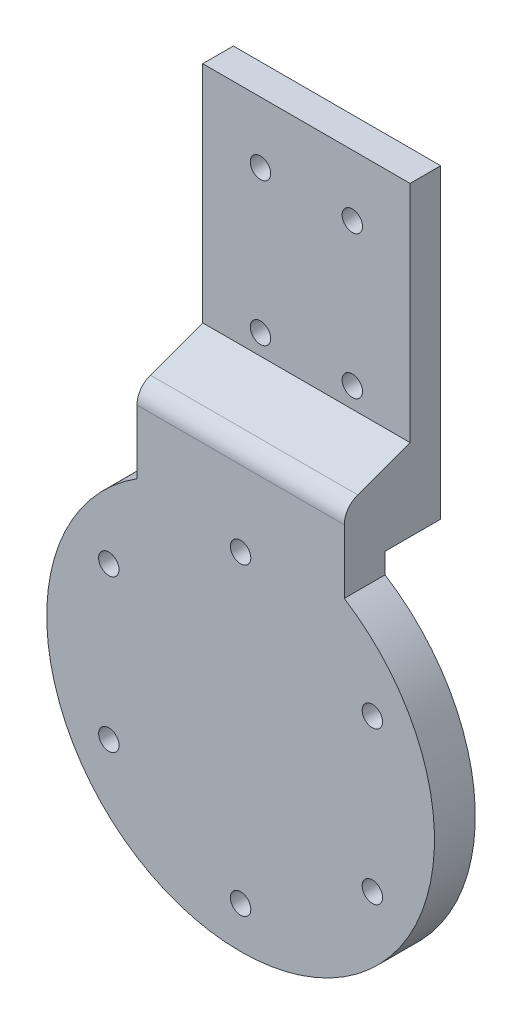
SolidWorks part; units mm, degrees
ref_plane "Front Plane" through (0, 0, 0) normal (0, 0, 1) x (1, 0, 0)
ref_plane "Top Plane" through (0, 0, 0) normal (0, 1, 0) x (1, 0, 0)
ref_plane "Right Plane" through (0, 0, 0) normal (1, 0, 0) x (0, 0, -1)
sketch "Sketch1" plane through (0, 0, 0) normal (0, 0, 1) x (1, 0, 0)
  line L0 (-25.4, 40.1384) -> (-25.4, 120.1384)
  line L1 (-25.4, 120.1384) -> (25.4, 120.1384)
  line L2 (25.4, 120.1384) -> (25.4, 40.1384)
  line L4 (-11.25, 105.1384) -> (11.25, 105.1384) construction
  line L5 (-11.25, 105.1384) -> (-11.25, 70.1384) construction
  line L6 (-11.25, 70.1384) -> (11.25, 70.1384) construction
  line L7 (11.25, 105.1384) -> (11.25, 70.1384) construction
  line L9 (-25.4, 45.1384) -> (25.4, 45.1384)
  line L10 (-25.4, 55.1384) -> (25.4, 55.1384)
  circle A2 centre (-11.25, 105.1384) radius 2.5
  circle A3 centre (11.25, 105.1384) radius 2.5
  circle A4 centre (11.25, 70.1384) radius 2.5
  circle A5 centre (-11.25, 70.1384) radius 2.5
  arc A6 (-25.4, 40.1384) -> (25.4, 40.1384) centre (0, 0) ccw
  circle A8 centre (0, 0) radius 37.28 construction
  circle A9 centre (0, 37.28) radius 2.5
  circle A10 centre (32.2854, 18.64) radius 2.5
  circle A11 centre (32.2854, -18.64) radius 2.5
  circle A12 centre (0, -37.28) radius 2.5
  circle A13 centre (-32.2854, -18.64) radius 2.5
  circle A14 centre (-32.2854, 18.64) radius 2.5
  point P2 (25.4, 40.1384)
  point P3 (0, 0)
  point P13 (0, 70.1384)
  point P32 (0, 0)
  point P35 (-25.4, 0)
  point P36 (-25.4, 0)
  point P37 (25.7058, 8.5415)
  point P38 (-26.525, 0)
  point P39 (0, 0)
  point P40 (0, 120.1384)
  dimension "D1" = 95
  dimension "D4" = 5
  dimension "D8" = 74.56
  dimension "D9" = 5
  dimension "D2" = 50.8
  dimension "D3" = 5
  dimension "D5" = 35
  dimension "D6" = 15
  dimension "D7" = 22.5
  dimension "D11" = 25
  dimension "D12" = 10
  dimension "D10" = 6
extrude "5" add sketch "Sketch1" along normal blind 7.5 contours L0 L9 L2 L1 A5 A4 A3 A2 region at (0, 87.6384, 0)
extrude "Boss-Extrude1" add sketch "Sketch1<3>" along normal blind 13.625 contours L10 L0 L9 L2 region at (0, 50.1384, 0)
sketch "Sketch1<3>" plane through (0, 0, 0) normal (0, 0, 1) x (1, 0, 0) same geometry as "Sketch1"
extrude "Boss-Extrude2" add sketch "Sketch1<4>" along normal blind 10 from surface contours A6 L2 L9 L0 A14 A13 A12 A11 A10 A9 | L10 L0 L9 L2 region at (0, -0.0136, 0) region at (0, 50.1384, 0) starting at face at (0, 50.1384, 13.625)
sketch "Sketch1<4>" plane through (0, 0, 0) normal (0, 0, 1) x (1, 0, 0) same geometry as "Sketch1"
chamfer "Chamfer1" distance 10 angle 70 1 edges at (0, 55.1384, 7.5) first distance on face at (-8.75, 70.1384, 7.5)
fillet "Fillet1" radius 5 1 edges at (0, 59.2694, 23.625)
